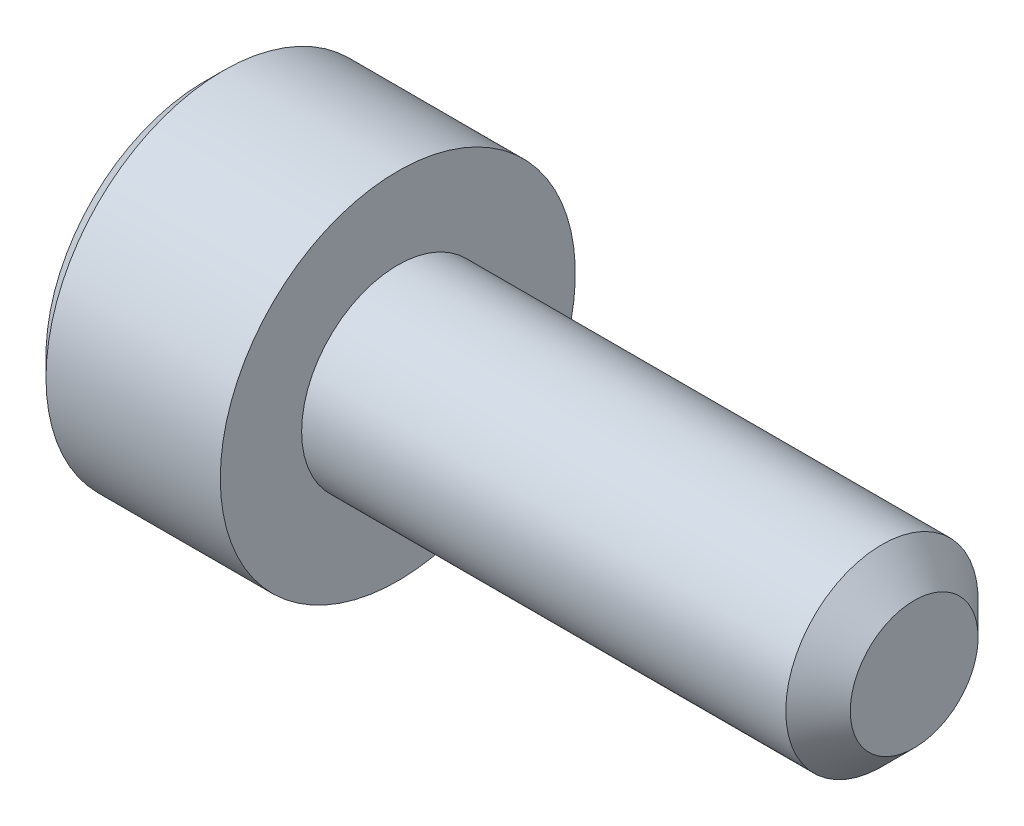
SolidWorks part; units mm, degrees
material "AISI Type 316L stainless steel"
ref_plane "Front Plane" through (0, 0, 0) normal (0, 0, 1) x (1, 0, 0)
ref_plane "Top Plane" through (0, 0, 0) normal (0, 1, 0) x (1, 0, 0)
ref_plane "Right Plane" through (0, 0, 0) normal (1, 0, 0) x (0, 0, -1)
sketch "Sketch1" plane through (0, 0, 0) normal (0, 0, 1) x (1, 0, 0)
  line L0 (-88.7055, 0) -> (96.9812, 0) construction
  line L1 (0, 0) -> (0, 2.75)
  line L2 (0, 2.75) -> (3, 2.75)
  line L4 (11, 0) -> (11, 1.49)
  line L5 (11, 1.49) -> (3, 1.49)
  line L6 (3, 1.49) -> (3, 2.75)
  line L7 (0, 0) -> (11, 0)
  dimension "D1" = 8
  dimension "D2" = 3
  dimension "D3" = 2.75
  dimension "D4" = 1.49
revolve "Revolve1" add sketch "Sketch1" angle 360 about L0
chamfer "Chamfer1" distance 0.5 angle 45 1 edges at (11, 0, 1.49)
chamfer "Chamfer2" distance 0.3 angle 45 1 edges at (0, 0, 2.75)
sketch "Sketch3" plane through (0, 0, 0) normal (1, 0, 0) x (0, 0, -1)
  line L1 (-1.4434, 0) -> (-0.7217, -1.25)
  line L2 (-0.7217, -1.25) -> (0.7217, -1.25)
  line L3 (0.7217, -1.25) -> (1.4434, 0)
  line L4 (1.4434, 0) -> (0.7217, 1.25)
  line L5 (0.7217, 1.25) -> (-0.7217, 1.25)
  line L6 (-0.7217, 1.25) -> (-1.4434, 0)
  circle A0 centre (0, 0) radius 1.25 construction
extrude "Cut-Extrude1" cut sketch "Sketch3" along normal blind 2.5
chamfer "Chamfer3" distance 0.3 angle 45 6 edges at (0, 1.25, 0) (0, 0.625, 1.0825) (0, -0.625, 1.0825) (0, -1.25, 0) (0, -0.625, -1.0825) (0, 0.625, -1.0825)
sketch "Sketch5" plane through (11, 0, 0) normal (1, 0, 0) x (0, 0, -1)
  circle A0 centre (0, 0) radius 1.49
curve "Helix/Spiral1" pitch 0.5 height 20 turns 40
sketch "Sketch8" plane through (0, 0, 0) normal (0, 1, 0) x (1, 0, 0)
  line L0 (11, 1.49) -> (11, 1.1111) construction
  line L1 (11.0625, 1.2194) -> (11.3281, 1.6794)
  line L2 (11.3281, 1.6794) -> (10.6719, 1.6794)
  line L3 (10.6719, 1.6794) -> (10.9375, 1.2194)
  line L4 (11, -0.99) -> (11, 0.99) construction
  circle A0 centre (11, 1.49) radius 0.1894 construction
  arc A1 (11.0625, 1.2194) -> (10.9375, 1.2194) centre (11, 1.2555) cw
  dimension "D2" = 0.0722
  dimension "D1" = 0.3789
sweep "Cut-Sweep1" [suppressed] cut profiles "Sketch8" path "Helix/Spiral1"
equation "\"length\"= 8"
equation "\"D1@Sketch1\"=\"length\""
